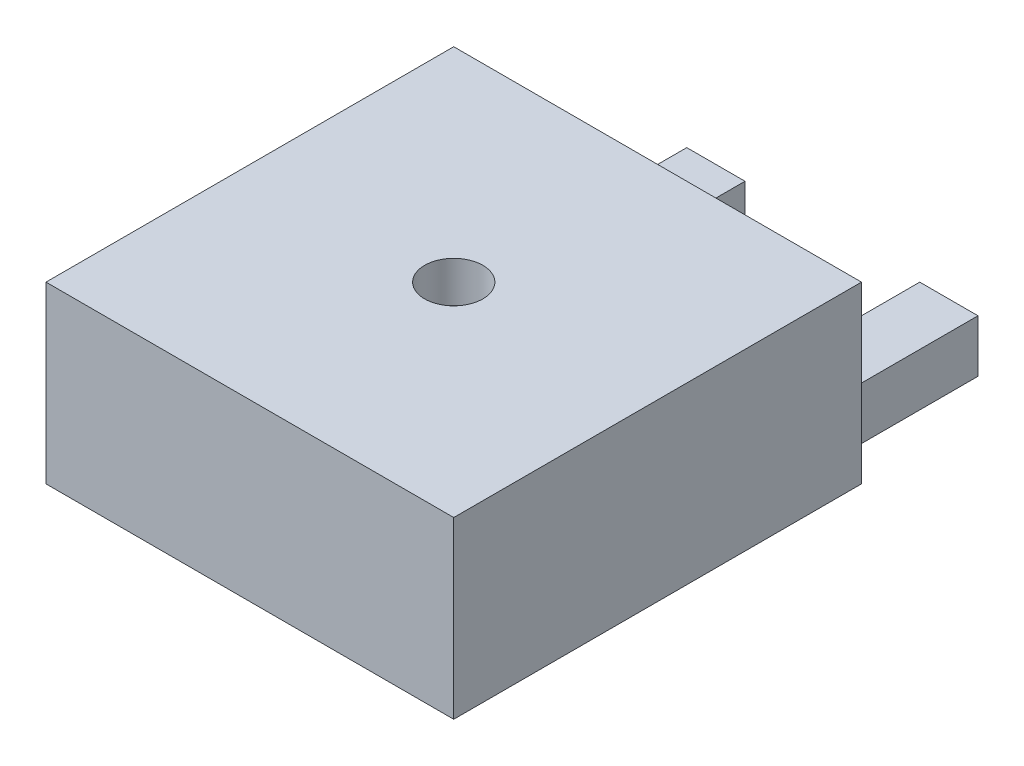
SolidWorks part; units mm, degrees
ref_plane "Plan de face" through (0, 0, 0) normal (0, 0, 1) x (1, 0, 0)
ref_plane "Plan de dessus" through (0, 0, 0) normal (0, 1, 0) x (1, 0, 0)
ref_plane "Plan de droite" through (0, 0, 0) normal (1, 0, 0) x (0, 0, -1)
sketch "Esquisse1" plane through (0, 0, 0) normal (0, 1, 0) x (1, 0, 0)
  line L1 (0, 0) -> (70, 0)
  line L2 (0, 0) -> (0, 70)
  line L3 (0, 70) -> (70, 70)
  line L4 (70, 0) -> (70, 70)
  dimension "D1" = 70
  dimension "D2" = 70
extrude "Boss.-Extru.4" add sketch "Esquisse1" along normal blind 30
sketch "Esquisse5" plane through (0, 0, 0) normal (0, -1, 0) x (-1, 0, 0)
  line L0 (-70, 0) -> (-70, 70) construction
  line L1 (-5, 5) -> (-65, 5)
  line L2 (-5, 5) -> (-5, 65)
  line L3 (-5, 65) -> (-65, 65)
  line L4 (-65, 5) -> (-65, 65)
  line L5 (0, 70) -> (0, 0) construction
  line L6 (0, 0) -> (-70, 0) construction
  line L7 (-70, 70) -> (0, 70) construction
  dimension "D1" = 5
  dimension "D2" = 5
  dimension "D3" = 5
  dimension "D4" = 5
extrude "Enlèv. mat.-Extru.3" cut sketch "Esquisse5" against normal blind 23
sketch "Esquisse6" plane through (0, 23, 0) normal (0, -1, 0) x (-1, 0, 0)
  line L0 (0, 0) -> (-70, 0) construction
  line L1 (0, 70) -> (0, 0) construction
  circle A0 centre (-35, 35) radius 5
  dimension "D1" = 10
  dimension "D2" = 35
  dimension "D3" = 35
extrude "Enlèv. mat.-Extru.4" cut sketch "Esquisse6" against normal blind 23 contours A0
sketch "Esquisse24" plane through (0, 0, -70) normal (0, 0, -1) x (-1, 0, 0)
  line L0 (0, 30) -> (-10.005, 30)
  line L1 (-70, 30) -> (0, 30) construction
  line L2 (-20.005, 30) -> (-50.005, 30)
  line L3 (-50.005, 30) -> (-60.005, 30)
  line L4 (-60.005, 30) -> (-60.005, 0)
  line L5 (-70, 0) -> (0, 0) construction
  line L10 (-60.005, 0) -> (-50.005, 0)
  line L11 (-50.005, 0) -> (-20.005, 0)
  line L12 (-20.005, 0) -> (-10.005, 0)
  dimension "D1" = 10
  dimension "D2" = 10.005
  dimension "D3" = 10
  dimension "D4" = 30
sketch "Esquisse28" plane through (0, 0, 0) normal (0, -1, 0) x (1, 0, 0)
  line L0 (50.005, -70) -> (60.005, -70) construction
  line L1 (50.005, -70) -> (60.005, -70)
  line L2 (50.005, -70) -> (50.005, -100)
  line L3 (50.005, -100) -> (60.005, -100)
  line L4 (60.005, -70) -> (60.005, -100)
  dimension "D1" = 30
extrude "Boss.-Extru.8" add sketch "Esquisse28" along normal mid plane 10
sketch "Esquisse29" plane through (60.005, 0, 0) normal (1, 0, 0) x (0, 0, -1)
  line L0 (70, -5) -> (85, -5)
  line L1 (100, -5) -> (96.4393, -14.671)
  line L2 (100, -5) -> (70, -5) construction
  line L3 (96.4393, -14.671) -> (98.2196, -9.8355)
  line L4 (98.2196, -9.8355) -> (97.3294, -12.2532)
  line L5 (97.3294, -12.2532) -> (85, -5)
  line M5 (70, -5) -> (100, -5)
extrude "Boss.-Extru.9" add sketch "Esquisse29" against normal blind 10 contours L5 L1 M5 region at (60.005, -7.4177, -94.1098)
sketch "Esquisse30" plane through (0, 0, 0) normal (0, -1, 0) x (1, 0, 0)
  line L0 (0, -70) -> (10.005, -70) construction
  line L1 (10.005, -70) -> (20.005, -70)
  line L2 (10.005, -70) -> (10.005, -100)
  line L3 (10.005, -100) -> (20.005, -100)
  line L4 (20.005, -70) -> (20.005, -100)
  dimension "D1" = 30
extrude "Boss.-Extru.10" add sketch "Esquisse30" along normal mid plane 10
sketch "Esquisse39" plane through (10.005, 0, 0) normal (-1, 0, 0) x (0, 0, 1)
  line L0 (-100, -5) -> (-95.9609, -15.2316)
  line L1 (-95.9609, -15.2316) -> (-85, -5)
  line L2 (-70, -5) -> (-100, -5) construction
  line L3 (-85, -5) -> (-100, -5)
  dimension "D1" = 11
extrude "Boss.-Extru.14" add sketch "Esquisse39" against normal blind 10
sketch "Esquisse40" plane through (0, -34.8279, -88.2251) normal (0, -0.3672, -0.9301) x (-1, 0, 0)
  line L0 (-20.005, 21.0679) -> (-20.005, 22.0679)
  line L1 (-20.005, 32.0679) -> (-20.005, 21.0679) construction
  line L2 (-20.005, 22.0679) -> (-10.005, 21.0679)
  line L3 (-10.005, 21.0679) -> (-20.005, 21.0679)
  dimension "D1" = 1
extrude "Enlèv. mat.-Extru.6" cut sketch "Esquisse40" against normal blind 10
sketch "Esquisse41" plane through (0, -33.0203, -89.6833) normal (0, -0.3455, -0.9384) x (-1, 0, 0)
  line L4 (-60.005, 23.13) -> (-60.005, 22.13)
  line L5 (-60.005, 29.8592) -> (-60.005, 22.13) construction
  line L6 (-60.005, 22.13) -> (-50.005, 22.13)
  line L7 (-50.005, 22.13) -> (-60.005, 23.13)
  dimension "D1" = 1
extrude "Enlèv. mat.-Extru.15" cut sketch "Esquisse41" against normal blind 14
sketch "Esquisse43" plane through (0, -33.0203, -89.6833) normal (0, -0.3455, -0.9384) x (-1, 0, 0)
  line L0 (-50.005, 29.8592) -> (-50.005, 23.3298)
  line L1 (-50.005, 29.8592) -> (-50.005, 22.13) construction
  line L2 (-50.005, 23.3298) -> (-60.005, 24.4475)
  line L3 (-60.005, 29.8592) -> (-60.005, 23.13) construction
  line L4 (-60.005, 24.4475) -> (-60.005, 29.8592)
  line L5 (-60.005, 29.8592) -> (-50.005, 29.8592)
  line L6 (-60.005, 23.13) -> (-60.005, 24.4475)
  line L7 (-50.005, 23.3298) -> (-50.005, 22.13)
  line L8 (-50.005, 22.13) -> (-60.005, 23.13)
  line M5 (-60.005, 29.8592) -> (-60.005, 23.13)
  line M6 (-60.005, 23.13) -> (-50.005, 22.13)
  line M7 (-50.005, 22.13) -> (-50.005, 29.8592)
  dimension "D1" = 6.5294
  dimension "D2" = 5.4118
extrude "Enlèv. mat.-Extru.16" cut sketch "Esquisse43" against normal blind 10 contours L2 M7 M5 M6 region at (55.0829, -11.1857, -97.7225)
sketch "Esquisse44" plane through (50.005, 0, 0) normal (-1, 0, 0) x (0, 0, 1)
  line L0 (-70, -5) -> (-70, -4.0027)
  line L1 (-70, -5) -> (-70, 0) construction
  line L2 (-70, -4.0027) -> (-84.9959, -4.0027)
  line L3 (-84.9959, -4.0027) -> (-97.744, -11.1273)
  line L4 (-97.744, -11.1273) -> (-91.5203, -8.8358)
  line L5 (-91.5203, -8.8358) -> (-85, -5)
  line L6 (-85, -5) -> (-70, -5)
extrude "Enlèv. mat.-Extru.17" cut sketch "Esquisse44" against normal blind 10
sketch "Esquisse45" plane through (0, -34.8279, -88.2251) normal (0, -0.3672, -0.9301) x (-1, 0, 0)
  line L0 (-20.005, 22.0679) -> (-20.005, 22.1856)
  line L1 (-20.005, 32.0679) -> (-20.005, 22.0679) construction
  line L2 (-20.005, 22.1856) -> (-10.005, 21.0679)
  line L3 (-10.005, 21.0679) -> (-20.005, 22.0679)
  dimension "D1" = 0.1176
extrude "Enlèv. mat.-Extru.18" cut sketch "Esquisse45" against normal blind 10
sketch "Esquisse47" plane through (10.005, 0, 0) normal (-1, 0, 0) x (0, 0, 1)
  line L0 (-85, -5) -> (-95.9609, -15.2316)
  line L1 (-95.9609, -15.2316) -> (-100, -5)
  line L2 (-100, -5) -> (-85, -5)
extrude "Enlèv. mat.-Extru.19" cut sketch "Esquisse47" against normal blind 10
sketch "Esquisse49" plane through (50.005, 0, 0) normal (-1, 0, 0) x (0, 0, 1)
  line L0 (-84.9959, -4.0027) -> (-100, -4.0027)
  line L1 (-100, -5) -> (-100, 5) construction
  line L2 (-100, -4.0027) -> (-100, -5)
  line L3 (-100, -5) -> (-97.744, -11.1273)
  line L4 (-97.744, -11.1273) -> (-84.9959, -4.0027)
extrude "Enlèv. mat.-Extru.20" cut sketch "Esquisse49" against normal blind 10
sketch "Esquisse51" plane through (0, 0, -100) normal (0, 0, -1) x (-1, 0, 0)
  line L0 (-10.005, -5) -> (-10.005, 5) construction
  line L1 (-20.005, -5) -> (-10.005, -5)
  line L2 (-20.005, -5) -> (-20.005, -4)
  line L3 (-20.005, -4) -> (-10.005, -4)
  line L4 (-10.005, -5) -> (-10.005, -4)
  dimension "D1" = 1
extrude "Enlèv. mat.-Extru.21" cut sketch "Esquisse51" against normal blind 37
